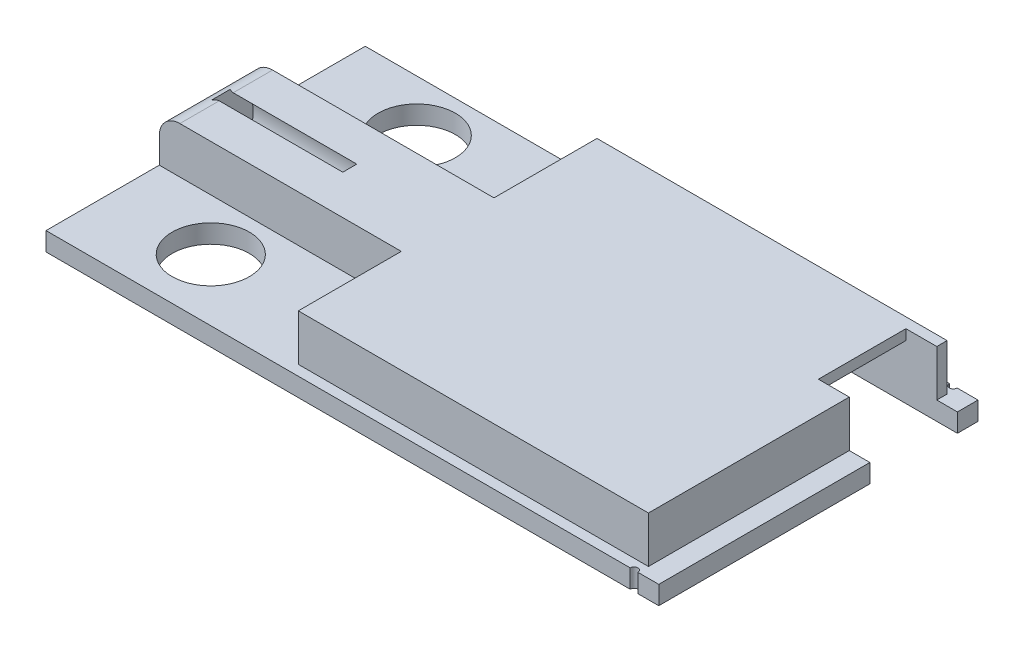
SolidWorks part; units mm, degrees
ref_plane "Plano frontal" through (0, 0, 0) normal (0, 0, 1) x (1, 0, 0)
ref_plane "Plano superior" through (0, 0, 0) normal (0, 1, 0) x (1, 0, 0)
ref_plane "Plano direito" through (0, 0, 0) normal (1, 0, 0) x (0, 0, -1)
sketch "Esboço1" plane through (0, 0, 0) normal (0, 1, 0) x (1, 0, 0)
  line L1 (0, 0) -> (119, 0)
  line L2 (0, 0) -> (0, 62)
  line L3 (0, 62) -> (119, 62)
  line L4 (119, 0) -> (119, 62)
  circle A0 centre (20, 52) radius 7.5
  circle A1 centre (20, 12) radius 7.5
  dimension "D5" = 15
  dimension "D6" = 15
  dimension "D1" = 62
  dimension "D2" = 119
  dimension "D3" = 10
  dimension "D4" = 40
  dimension "D7" = 20
  dimension "D8" = 20
extrude "Ressalto-extrusão1" add sketch "Esboço1" along normal blind 3 and the other way blind 0.6
sketch "Esboço2" plane through (0, 3, 0) normal (0, 1, 0) x (1, 0, 0)
  line L0 (0, 0) -> (119, 0) construction
  line L1 (47, 2) -> (115, 2)
  line L2 (47, 2) -> (47, 22)
  line L3 (47, 60) -> (115, 60)
  line L4 (115, 2) -> (115, 60)
  line L5 (119, 0) -> (119, 62) construction
  line L6 (47, 40) -> (47, 60)
  line L7 (0, 22) -> (47, 22)
  line L8 (0, 22) -> (0, 40)
  line L9 (0, 40) -> (47, 40)
  line L11 (0, 62) -> (0, 0) construction
  dimension "D1" = 58
  dimension "D2" = 68
  dimension "D3" = 2
  dimension "D4" = 4
  dimension "D5" = 0
  dimension "D6" = 18
  dimension "D7" = 20
extrude "Ressalto-extrusão2" add sketch "Esboço2" along normal blind 9
sketch "Esboço3" plane through (0, 12, 0) normal (0, 1, 0) x (1, 0, 0)
  line L0 (47, 22) -> (47, 2) construction
  line L1 (49, 58) -> (113, 58)
  line L2 (49, 58) -> (49, 37)
  line L3 (49, 4) -> (113, 4)
  line L4 (113, 58) -> (113, 4)
  line L5 (115, 2) -> (115, 60) construction
  line L6 (115, 60) -> (47, 60) construction
  line L7 (47, 2) -> (115, 2) construction
  line L8 (49, 25) -> (49, 4)
  line L9 (3, 25) -> (49, 25)
  line L10 (3, 25) -> (3, 37)
  line L11 (3, 37) -> (49, 37)
  line L13 (47, 40) -> (0, 40) construction
  line L14 (0, 22) -> (47, 22) construction
  line L15 (0, 40) -> (0, 22) construction
  point P22 (0, 31)
  dimension "D1" = 2
  dimension "D2" = 2
  dimension "D3" = 2
  dimension "D4" = 2
  dimension "D5" = 3
  dimension "D6" = 3
  dimension "D7" = 3
extrude "Corte-extrusão1" cut sketch "Esboço3" against normal through all from offset 2 offset against normal yes
sketch "Esboço4" plane through (0, 0, 0) normal (-1, 0, 0) x (0, 0, 1)
  line L1 (-40, 12) -> (-40, 3) construction
  line L2 (-62, -0.6) -> (0, -0.6) construction
  circle A0 centre (-31, 5.9) radius 3
  circle A1 centre (-31, 5.9) radius 6.25
  dimension "D1" = 6
  dimension "D2" = 12.5
  dimension "D3" = 9
  dimension "D4" = 6.5
extrude "Corte-extrusão2" cut sketch "Esboço4" against normal blind 28 contours A0
extrude "Corte-extrusão3" cut sketch "Esboço4<4>" against normal blind 25 from surface starting at face at (3, 5.9, -28)
sketch "Esboço4<4>" plane through (0, 0, 0) normal (-1, 0, 0) x (0, 0, 1) same geometry as "Esboço4"
sketch "Esboço6" plane through (0, -0.6, 0) normal (0, -1, 0) x (1, 0, 0)
  line L0 (0, 0) -> (119, 0) construction
  line L1 (119, -62) -> (0, -62) construction
  line L2 (119, 0) -> (119, -62) construction
  line L3 (119, 0) -> (119, -62) construction
  circle A0 centre (114.2, 0) radius 0.75
  circle A1 centre (114.2, -62) radius 0.75
  dimension "D1" = 1.5
  dimension "D2" = 1.5
  dimension "D3" = 4.8
  dimension "D4" = 4.8
extrude "Corte-extrusão5" cut sketch "Esboço6" against normal up to surface (3.6 mm away) up to face at (20, 3, -4.5)
sketch "Esboço7" plane through (0, -0.6, 0) normal (0, -1, 0) x (-1, 0, 0)
  line L0 (-119, 0) -> (-119, 62) construction
  line L1 (-119, 58) -> (-109, 58)
  line L2 (-119, 58) -> (-119, 41)
  line L3 (-119, 41) -> (-109, 41)
  line L4 (-109, 58) -> (-109, 41)
  line L6 (-119, 62) -> (-114.95, 62) construction
  dimension "D1" = 10
  dimension "D2" = 17
  dimension "D3" = 4
extrude "Corte-extrusão6" cut sketch "Esboço7" against normal up to surface (12.6 mm away) up to face at (52.25, 12, -31)
fillet "Filete1" radius 4 1 edges at (0, 12, -31)
